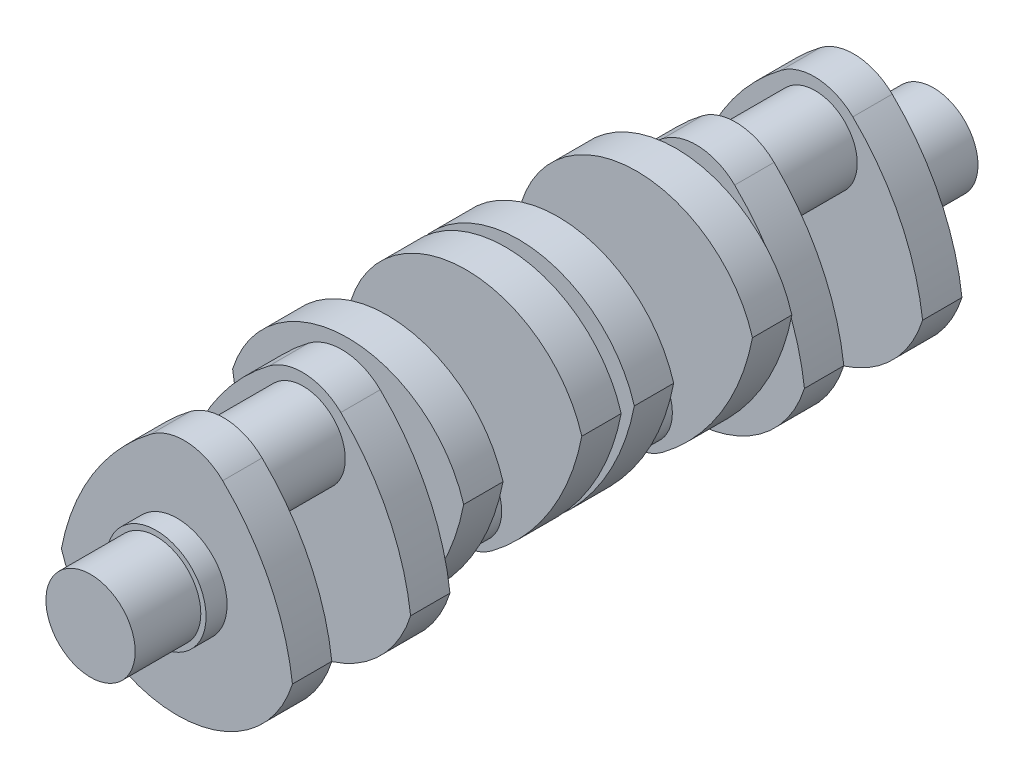
SolidWorks part; units mm, degrees
ref_plane "Front Plane" through (0, 0, 0) normal (0, 0, 1) x (1, 0, 0)
ref_plane "Top Plane" through (0, 0, 0) normal (0, 1, 0) x (1, 0, 0)
ref_plane "Right Plane" through (0, 0, 0) normal (1, 0, 0) x (0, 0, -1)
sketch "Sketch1" plane through (0, 0, 0) normal (0, 0, 1) x (1, 0, 0)
  circle A0 centre (0, 0) radius 19
  circle A1 centre (0, 0) radius 17
  dimension "D1" = 38
  dimension "D2" = 34
extrude "Boss-Extrude1" add sketch "Sketch1" against normal blind 25 contours A1
extrude "Boss-Extrude2" add sketch "Sketch1<3>" along normal blind 8 contours A0
sketch "Sketch1<3>" plane through (0, 0, 0) normal (0, 0, 1) x (1, 0, 0) same geometry as "Sketch1"
sketch "Sketch2" plane through (0, 0, 8) normal (0, 0, 1) x (1, 0, 0)
  arc A0 (-9.9861, 41.7528) -> (17.3303, 40.0423) centre (2.6767, 25) cw
  arc A1 (-44.1028, -13.0747) -> (43.8946, -13.7574) centre (0, 0) ccw
  arc A2 (-9.9861, 41.7528) -> (-44.1028, -13.0747) centre (44.2828, -30.0448) ccw
  arc A3 (17.3303, 40.0423) -> (43.8946, -13.7574) centre (-45.471, -24.4247) cw
  dimension "D3" = 21
  dimension "D4" = 46
  dimension "D5" = 90
  dimension "D6" = 88
  dimension "D2" = 90
  dimension "D1" = 25
extrude "Boss-Extrude3" add sketch "Sketch2" along normal blind 15
sketch "Sketch3" plane through (0, 0, 23) normal (0, 0, 1) x (1, 0, 0)
  circle A0 centre (3.01, 25.5498) radius 16
  point P2 (3.01, 25.5498)
  dimension "D1" = 32
extrude "Boss-Extrude4" add sketch "Sketch3" along normal blind 15
mirror "Mirror1" about plane through (3.01, 25.5498, 38) normal (0, 0, 1) of "Boss-Extrude3", "Boss-Extrude4"
sketch "Sketch4" plane through (0, 0, 68) normal (0, 0, 1) x (1, 0, 0)
  circle A0 centre (0, 0) radius 16
  dimension "D1" = 32
extrude "Boss-Extrude5" add sketch "Sketch4" along normal blind 5
sketch "Sketch5" plane through (0, 0, 73) normal (0, 0, 1) x (1, 0, 0)
  arc A8 (-17.3303, -40.0423) -> (9.9861, -41.7528) centre (-2.6767, -25) ccw
  arc A9 (-43.8946, 13.7574) -> (-17.3303, -40.0423) centre (45.471, 24.4247) ccw
  arc A10 (44.1028, 13.0747) -> (-43.8946, 13.7574) centre (0, 0) ccw
  arc A11 (9.9861, -41.7528) -> (44.1028, 13.0747) centre (-44.2828, 30.0448) ccw
extrude "Boss-Extrude6" add sketch "Sketch5" along normal blind 15
sketch "Sketch6" plane through (0, 0, 88) normal (0, 0, 1) x (1, 0, 0)
  circle A0 centre (-2.4064, -26.9653) radius 16
  point P2 (0, 0)
  point P3 (-2.4064, -26.9653)
  dimension "D1" = 32
extrude "Boss-Extrude7" add sketch "Sketch6" along normal blind 15
mirror "Mirror2" about plane through (-2.4064, -26.9653, 103) normal (0, 0, 1) of "Boss-Extrude6", "Boss-Extrude7"
sketch "Sketch7" plane through (0, 0, 133) normal (0, 0, 1) x (1, 0, 0)
  circle A0 centre (0, 0) radius 17
  dimension "D1" = 34
extrude "Boss-Extrude8" add sketch "Sketch7" along normal blind 2.5
mirror "Mirror3" about plane through (0, 0, 135.5) normal (0, 0, 1) of bodies 110
